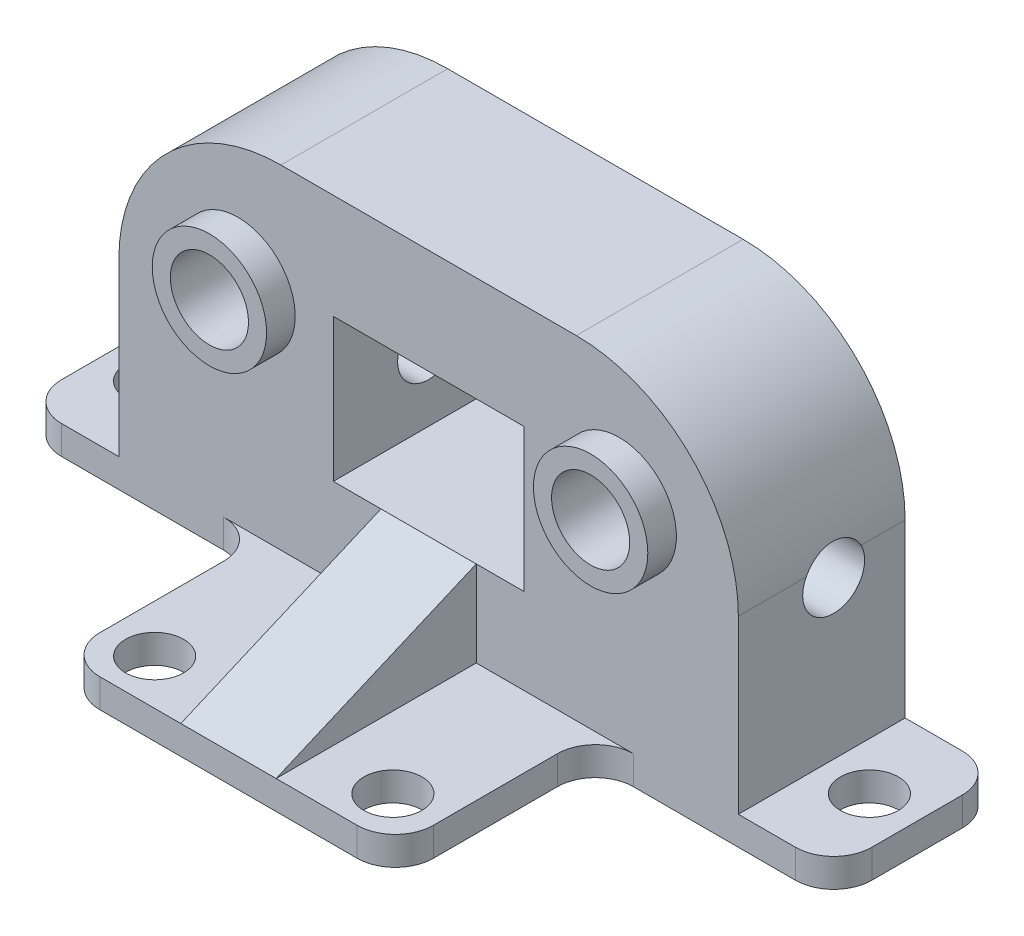
SolidWorks part; units mm, degrees
ref_plane "Přední rovina" through (0, 0, 0) normal (0, 0, 1) x (1, 0, 0)
ref_plane "Vrchní rovina" through (0, 0, 0) normal (0, 1, 0) x (1, 0, 0)
ref_plane "Pravá rovina" through (0, 0, 0) normal (1, 0, 0) x (0, 0, -1)
sketch "Skica1" plane through (0, 0, 0) normal (0, 1, 0) x (1, 0, 0)
  line L1 (-42.5, 8.75) -> (42.5, 8.75)
  line L2 (-42.5, 8.75) -> (-42.5, -8.75)
  line L3 (-42.5, -8.75) -> (42.5, -8.75)
  line L4 (42.5, 8.75) -> (42.5, -8.75)
  line L5 (-42.5, 8.75) -> (42.5, -8.75) construction
  line L6 (-42.5, -8.75) -> (42.5, 8.75) construction
  line L7 (37.5, 0) -> (-37.5, 0) construction
  circle A1 centre (-37.5, 0) radius 3.05
  circle A3 centre (37.5, 0) radius 3.05
  point P0 (0, 0)
  point P8 (0, 0)
  dimension "D3" = 75
  dimension "D4" = 6.1
  dimension "D1" = 85
  dimension "D2" = 17.5
extrude "Přidat vysunutím1" add sketch "Skica1" along normal blind 3
sketch "Skica3" plane through (0, 0, 8.75) normal (0, 0, 1) x (1, 0, 0)
  line L0 (-42.5, 3) -> (42.5, 3) construction
  line L1 (-32.5, 38) -> (32.5, 38)
  line L2 (-32.5, 38) -> (-32.5, 3)
  line L3 (-32.5, 3) -> (32.5, 3)
  line L4 (32.5, 38) -> (32.5, 3)
  line L5 (-32.5, 38) -> (32.5, 3) construction
  line L6 (-32.5, 3) -> (32.5, 38) construction
  line L7 (0, 20.5) -> (0, 0) construction
  line L8 (-42.5, 0) -> (42.5, 0) construction
  point P0 (0, 20.5)
  dimension "D1" = 65
  dimension "D2" = 35
extrude "Přidat vysunutím2" add sketch "Skica3" against normal blind 17.5
fillet "Zaoblit2" radius 17 2 edges at (-32.5, 38, 0) (32.5, 38, 0)
sketch "Skica4" plane through (0, 0, 8.75) normal (0, 0, 1) x (1, 0, 0)
  line L0 (-20, 25) -> (20, 25) construction
  line L1 (-42.5, 0) -> (42.5, 0) construction
  line L2 (0, 25) -> (0, 0) construction
  circle A0 centre (-20, 25) radius 4.1
  circle A1 centre (20, 25) radius 4.1
  circle A2 centre (-20, 25) radius 6
  circle A3 centre (20, 25) radius 6
  point P6 (0, 0)
  dimension "D2" = 8.2
  dimension "D3" = 8.2
  dimension "D4" = 12
  dimension "D5" = 12
  dimension "D1" = 25
  dimension "D6" = 40
extrude "Přidat vysunutím3" add sketch "Skica4" along normal blind 3
extrude "Odebrat vysunutím1" cut sketch "Skica4<2>" against normal blind 4 contours A1 | A0 region at (-20, 25, 8.75) region at (20, 25, 8.75)
sketch "Skica4<2>" plane through (0, 0, 8.75) normal (0, 0, 1) x (1, 0, 0) same geometry as "Skica4"
sketch "Skica5" plane through (0, 0, 8.75) normal (0, 0, 1) x (1, 0, 0)
  line L0 (0, 0) -> (0, 19.5) construction
  line L1 (-10, 27) -> (10, 27)
  line L2 (-10, 27) -> (-10, 12)
  line L3 (-10, 12) -> (10, 12)
  line L4 (10, 27) -> (10, 12)
  line L5 (-10, 27) -> (10, 12) construction
  line L6 (-10, 12) -> (10, 27) construction
  line L7 (-42.5, 0) -> (42.5, 0) construction
  circle A0 centre (-20, 25) radius 4.1 construction
  circle A1 centre (-20, 25) radius 4.1 construction
  point P0 (0, 19.5)
  dimension "D1" = 20
  dimension "D2" = 15
  dimension "D3" = 2
extrude "Odebrat vysunutím2" cut sketch "Skica5" against normal through all
sketch "Skica7" plane through (32.5, 0, 0) normal (1, 0, 0) x (0, 0, -1)
  line L0 (-8.75, 27) -> (-8.75, 12) construction
  line L1 (-8.75, 27) -> (-8.75, 12) construction
  line L2 (-8.75, 19.5) -> (11.25, 19.5) construction
  circle A0 centre (1.25, 19.5) radius 3.25
  dimension "D1" = 6.5
  dimension "D2" = 10
extrude "Odebrat vysunutím4" cut sketch "Skica7" against normal blind 50
sketch "Skica8" plane through (0, 0, 0) normal (0, -1, 0) x (1, 0, 0)
  line L0 (-17.5, 8.75) -> (-17.5, 29.75)
  line L2 (-17.5, 29.75) -> (17.5, 29.75)
  line L3 (17.5, 29.75) -> (17.5, 8.75)
  line L4 (17.5, 8.75) -> (-17.5, 8.75)
  line L5 (0, 8.75) -> (0, 0) construction
  line L6 (-42.5, 8.75) -> (42.5, 8.75) construction
  circle A0 centre (-12.5, 25) radius 3.05
  circle A1 centre (-37.5, 0) radius 3.05 construction
  circle A2 centre (-37.5, 0) radius 3.05 construction
  circle A3 centre (12.5, 25) radius 3.05
  dimension "D1" = 6.1
  dimension "D2" = 25
  dimension "D3" = 25
  dimension "D4" = 21
  dimension "D5" = 35
extrude "Přidat vysunutím4" add sketch "Skica8" against normal blind 3
fillet "Zaoblit1" radius 4 8 edges at (42.5, 1.5, 8.75) (42.5, 1.5, -8.75) (-42.5, 1.5, -8.75) (-42.5, 1.5, 8.75) (17.5, 1.5, 8.75) (-17.5, 1.5, 8.75) (-17.5, 1.5, 29.75) (17.5, 1.5, 29.75)
sketch "Skica12" plane through (0, 0, 0) normal (1, 0, 0) x (0, 0, -1)
  line L0 (-29.75, 3) -> (-8.75, 12)
rib "Žebro4" sketch "Skica12" sketch "Skica12" thickness 10 extrusion direction parallel to sketch draft on no parameters "D1"=10
